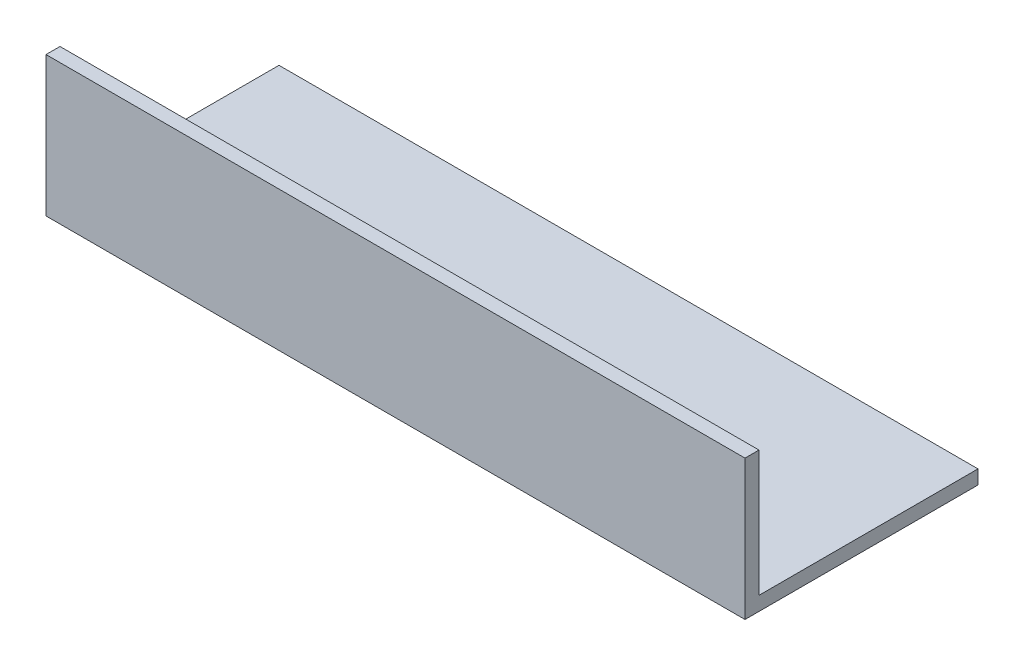
SolidWorks part; units mm, degrees
ref_plane "Спереди" through (0, 0, 0) normal (0, 0, 1) x (1, 0, 0)
ref_plane "Сверху" through (0, 0, 0) normal (0, 1, 0) x (1, 0, 0)
ref_plane "Справа" through (0, 0, 0) normal (1, 0, 0) x (0, 0, -1)
sketch "Эскиз1" plane through (0, 0, 0) normal (1, 0, 0) x (0, 0, -1)
  line L0 (0, 0) -> (0, 30)
  line L1 (0, 0) -> (50, 0)
extrude "Вытянуть-Тонкостенный1" add sketch "Эскиз1" along normal blind 150 thin thin type one direction reverse wall 3
